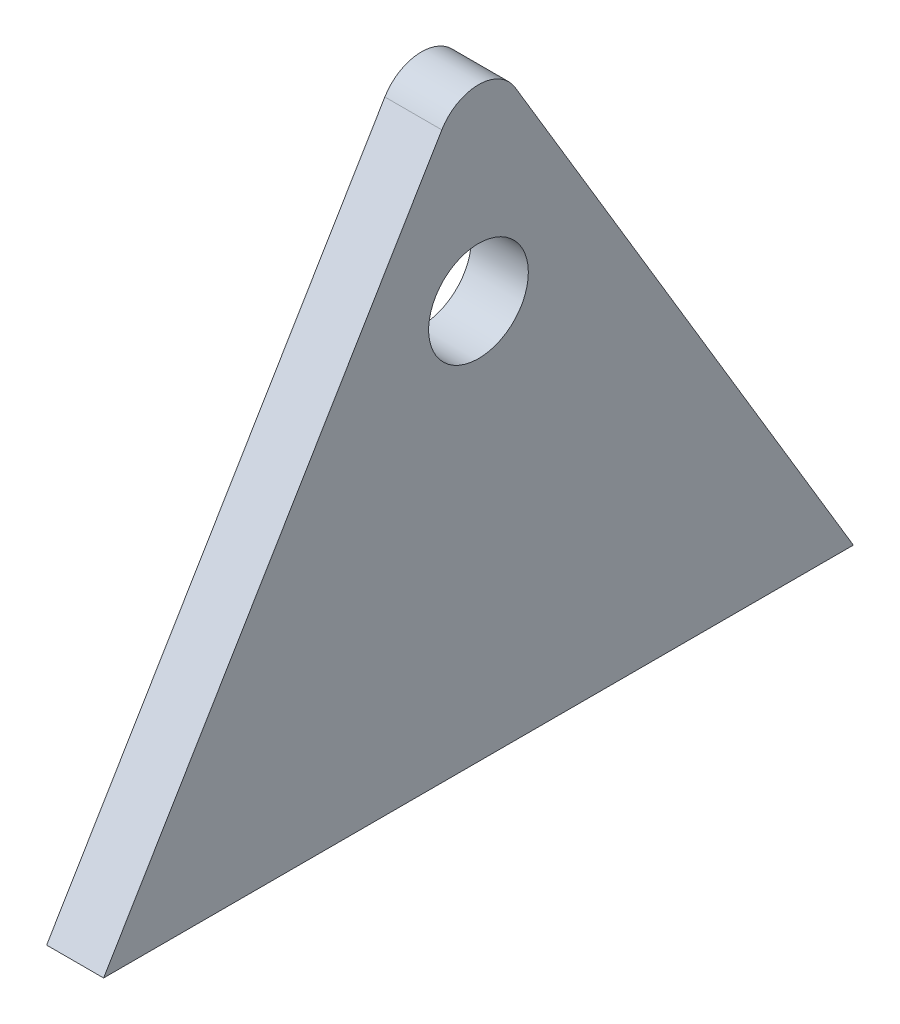
SolidWorks part; units mm, degrees
material "Pine"
ref_plane "Front Plane" through (0, 0, 0) normal (0, 0, 1) x (1, 0, 0)
ref_plane "Top Plane" through (0, 0, 0) normal (0, 1, 0) x (1, 0, 0)
ref_plane "Right Plane" through (0, 0, 0) normal (1, 0, 0) x (0, 0, -1)
sketch "Sketch1" plane through (0, 0, 0) normal (1, 0, 0) x (0, 0, -1)
  line L0 (0, 0) -> (0, 139.7) construction
  line L1 (0, 139.7) -> (-83.564, 0)
  line L2 (-83.564, 0) -> (83.564, 0)
  line L3 (0, 139.7) -> (83.564, 0)
  dimension "D1" = 139.7
  dimension "D2" = 30.887
extrude "Boss-Extrude1" add sketch "Sketch1" along normal blind 12.7
fillet "Fillet1" radius 9.525 1 edges at (6.35, 139.7, 0)
sketch "Sketch2" plane through (0, 0, 0) normal (1, 0, 0) x (0, 0, -1)
  line L0 (0, 0) -> (0, 88.9) construction
  circle A0 centre (0, 88.9) radius 11.1125
  dimension "D2" = 22.225
  dimension "D1" = 88.9
extrude "Cut-Extrude3" cut sketch "Sketch2" against normal through all and the other way through all
